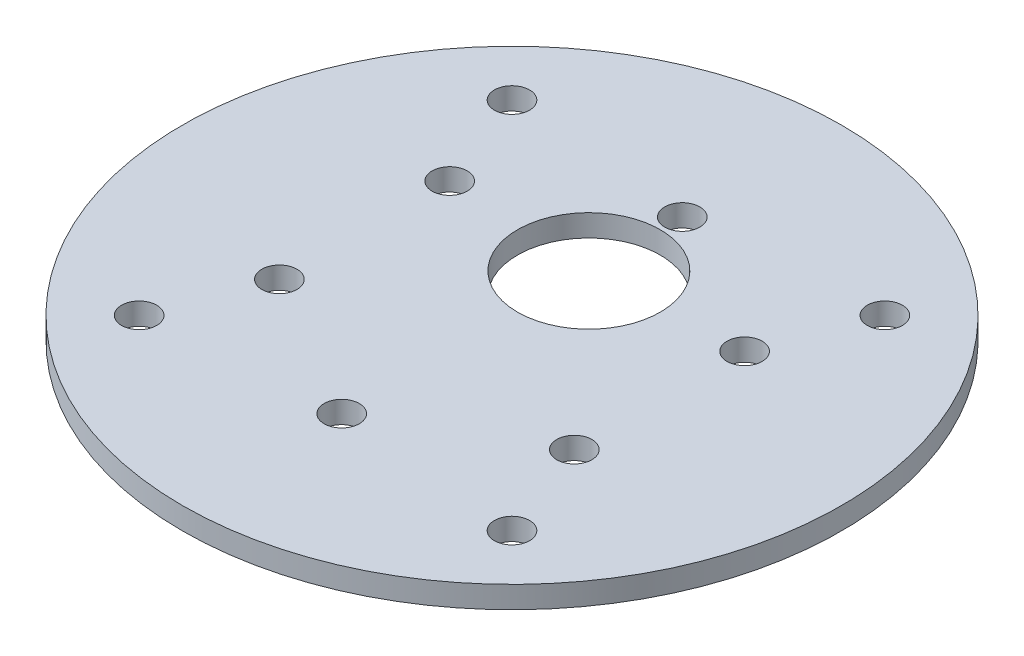
SolidWorks part; units mm, degrees
ref_plane "前视基准面" through (0, 0, 0) normal (0, 0, 1) x (1, 0, 0)
ref_plane "上视基准面" through (0, 0, 0) normal (0, 1, 0) x (1, 0, 0)
ref_plane "右视基准面" through (0, 0, 0) normal (1, 0, 0) x (0, 0, -1)
sketch "草图1" plane through (0, 0, 0) normal (0, 1, 0) x (1, 0, 0)
  line L0 (0, 0) -> (21.2132, -21.2132) construction
  line L1 (0, 0) -> (30, 0) construction
  circle A0 centre (0, 0) radius 30
  circle A3 centre (0, 7) radius 6.5
  circle A5 centre (0, 15.5) radius 1.6
  circle A6 centre (13.4234, 7.75) radius 1.6
  circle A7 centre (13.4234, -7.75) radius 1.6
  circle A8 centre (0, -15.5) radius 1.6
  circle A9 centre (-13.4234, -7.75) radius 1.6
  circle A10 centre (-13.4234, 7.75) radius 1.6
  circle A11 centre (0, 7) radius 6 construction
  circle A12 centre (16.9706, -16.9706) radius 1.6
  circle A13 centre (-16.9706, -16.9706) radius 1.6
  circle A14 centre (-16.9706, 16.9706) radius 1.6
  circle A15 centre (16.9706, 16.9706) radius 1.6
  point P23 (0, 0)
  point P35 (0, 0)
  dimension "D1" = 0.5
  dimension "D2" = 60
  dimension "D3" = 3.2
  dimension "D6" = 3.2
  dimension "D5" = 45
  dimension "D7" = 6
  dimension "D4" = 6
  dimension "D8" = 4
extrude "凸台-拉伸1" add sketch "草图1" along normal blind 2
